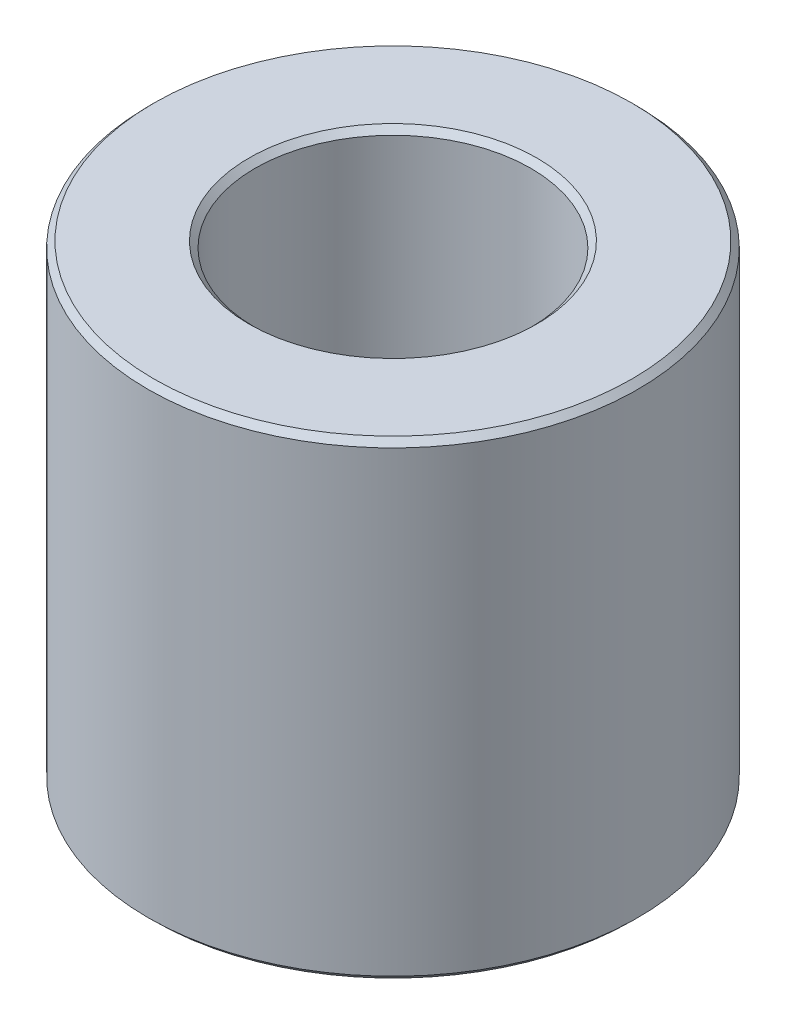
SolidWorks part; units mm, degrees
ref_plane "Front Plane" through (0, 0, 0) normal (0, 0, 1) x (1, 0, 0)
ref_plane "Top Plane" through (0, 0, 0) normal (0, 1, 0) x (1, 0, 0)
ref_plane "Right Plane" through (0, 0, 0) normal (1, 0, 0) x (0, 0, -1)
sketch "Sketch1" plane through (0, 0, 0) normal (0, 1, 0) x (1, 0, 0)
  circle A0 centre (0, 0) radius 50
  dimension "SLEEVE_OD" = 100
extrude "Boss-Extrude1" add sketch "Sketch1" along normal blind 95.8478
sketch "Sketch2" plane through (0, 0, 0) normal (0, 1, 0) x (1, 0, 0)
  circle A0 centre (0, 0) radius 28.1485
  dimension "BORE_D" = 56.297
extrude "Cut-Extrude1" cut sketch "Sketch2" along normal through all
chamfer "Chamfer1" distance 1.2347 angle 44.296 4 edges at (0, 95.8478, 28.1485) (0, 0, 28.1485) (0, 0, 50) (0, 95.8478, 50) first distance on face at (0, 95.8478, 28.1485) first distance on face at (0, 0, 28.1485) first distance on face at (0, 95.8478, 50)
